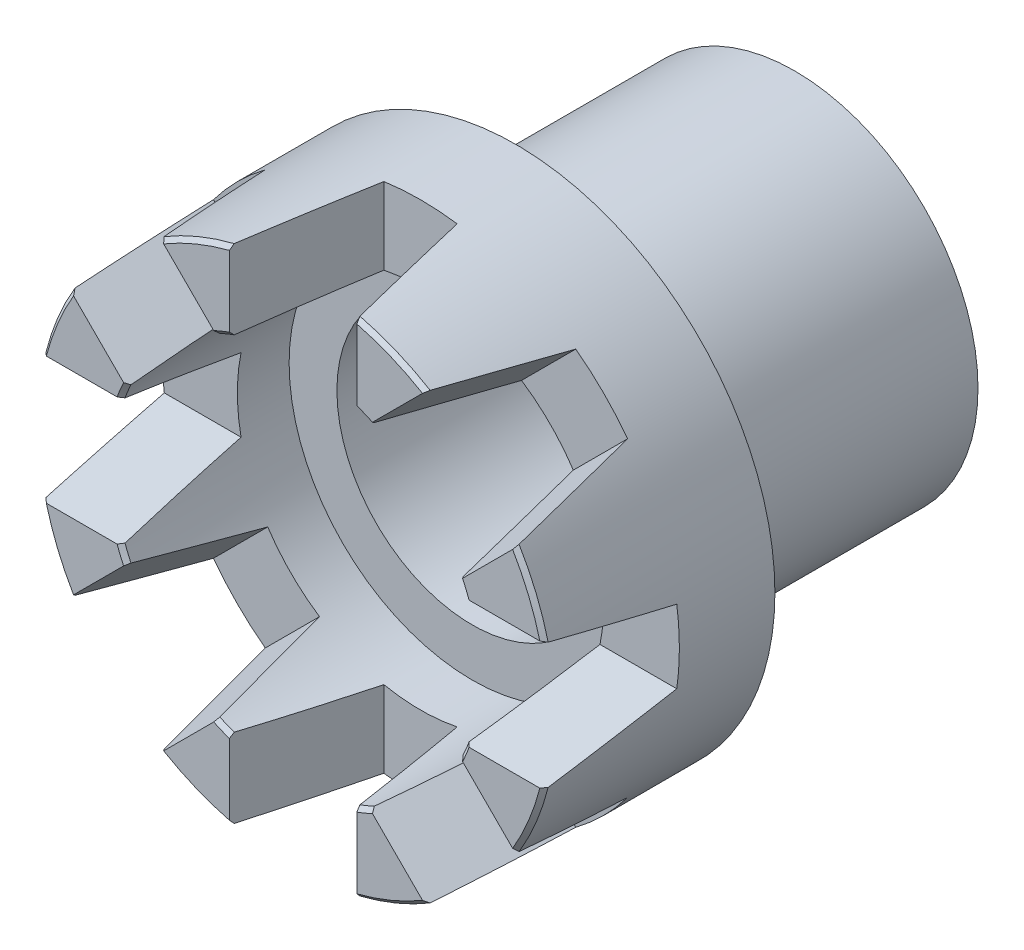
SolidWorks part; units mm, degrees
ref_plane "Спереди" through (0, 0, 0) normal (0, 0, 1) x (1, 0, 0)
ref_plane "Сверху" through (0, 0, 0) normal (0, 1, 0) x (1, 0, 0)
ref_plane "Справа" through (0, 0, 0) normal (1, 0, 0) x (0, 0, -1)
sketch "Эскиз1" plane through (0, 0, 0) normal (1, 0, 0) x (0, 0, -1)
  line L0 (0, 46) -> (0, 65)
  line L1 (0, 65) -> (56, 65)
  line L2 (56, 65) -> (56, 46)
  line L3 (56, 46) -> (126, 46)
  line L4 (126, 46) -> (126, 32)
  line L5 (126, 32) -> (123, 32)
  line L6 (123, 32) -> (123, 34)
  line L7 (123, 34) -> (45, 34)
  line L8 (45, 34) -> (45, 46)
  line L9 (45, 46) -> (0, 46)
  line L10 (0, 0) -> (130, 0) construction
revolve "Повернуть1" add sketch "Эскиз1" angle 360 about L10
ref_plane "Плоскость1" through (0, 65, -28) normal (0, 1, 0) x (-1, 0, 0)
chamfer "Фаска1" distance 1 angle 45 2 edges at (65, 0, 0) (46, 0, 0)
sketch "Эскиз2" plane through (0, 65, -28) normal (0, 1, 0) x (-1, 0, 0)
  line L0 (0, 28) -> (0, -22) construction
  line L1 (16, 28) -> (-16, 28)
  line L2 (46, 28) -> (-46, 28) construction
  line L3 (-16, 28) -> (-9.1982, -4)
  line L4 (-9.1982, -4) -> (9.1982, -4)
  line L5 (16, 28) -> (9.1982, -4)
  point P10 (0, -4)
extrude "Вырез-Вытянуть1" cut sketch "Эскиз2" against normal blind 65
ref_axis "Ось1" through (0, 0, -45) along (0, 0, 1)
pattern_circular "Круговой массив1" count 8 over 360 about axis through (0, 0, -45) along (0, 0, 1) of "Вырез-Вытянуть1"
